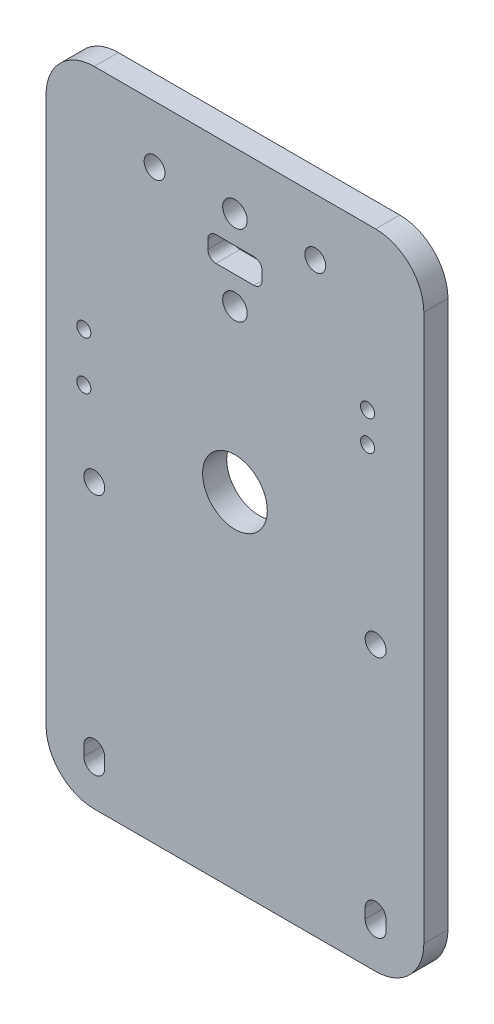
SolidWorks part; units mm, degrees
material "Acrylic (Medium-high impact)"
ref_plane "Спереди" through (0, 0, 0) normal (0, 0, 1) x (1, 0, 0)
ref_plane "Сверху" through (0, 0, 0) normal (0, 1, 0) x (1, 0, 0)
ref_plane "Справа" through (0, 0, 0) normal (1, 0, 0) x (0, 0, -1)
sketch "Model" plane through (0, 0, 0) normal (0, 0, 1) x (1, 0, 0)
  line L5 (0, 170.1561) -> (0, 0) construction
  line L24 (-35, 37.2847) -> (-35, 78.8619) construction
  line L25 (-31.4983, 12.5) -> (-38.4, 12.5) construction
  line L26 (-31.4983, 10) -> (-38.4, 10) construction
  line L27 (-35, 12.5) -> (-35, 10) construction
  line L28 (-32.4, 12.5) -> (-32.4, 10)
  line L29 (-37.6, 12.5) -> (-37.6, 10)
  line L40 (31.4983, 10) -> (38.4, 10) construction
  line L41 (31.4983, 12.5) -> (38.4, 12.5) construction
  line L42 (35, 37.2847) -> (35, 78.8619) construction
  line L43 (35, 12.5) -> (35, 10) construction
  line L44 (32.4, 12.5) -> (32.4, 10)
  line L45 (37.6, 12.5) -> (37.6, 10)
  line L47 (-26.0102, 145.8) -> (26.0946, 145.8) construction
  line L50 (-20, 133.6948) -> (-20, 127.8457) construction
  line L51 (-38.85, 70.45) -> (-29.8907, 70.45) construction
  line L53 (-16.3166, 125.8) -> (17.7871, 125.8) construction
  line L58 (38.85, 70.45) -> (29.8907, 70.45) construction
  line L4875 (-35, 160) -> (35, 160)
  line L4882 (47, 148) -> (47, 12)
  line L4889 (35, 0) -> (-35, 0)
  line L4896 (-47, 12) -> (-47, 148)
  line L6648 (-6.75, 138.9) -> (6.75, 138.9)
  line L6649 (6.75, 138.9) -> (6.75, 132.7)
  line L6650 (6.75, 132.7) -> (-6.75, 132.7)
  line L6651 (-6.75, 132.7) -> (-6.75, 138.9)
  arc A0 (-47, 12) -> (-35, 0) centre (-35, 12) ccw
  arc A1 (35, 0) -> (47, 12) centre (35, 12) ccw
  arc A2 (47, 148) -> (35, 160) centre (35, 148) ccw
  arc A3 (-35, 160) -> (-47, 148) centre (-35, 148) ccw
  arc A13 (-32.4, 12.5) -> (-37.6, 12.5) centre (-35, 12.5) ccw
  arc A14 (-37.6, 10) -> (-32.4, 10) centre (-35, 10) ccw
  arc A19 (32.4, 12.5) -> (37.6, 12.5) centre (35, 12.5) cw
  arc A20 (37.6, 10) -> (32.4, 10) centre (35, 10) cw
  circle A29 centre (0, 145.8) radius 3.05
  circle A30 centre (-20, 145.8) radius 2.6
  circle A31 centre (20, 145.8) radius 2.6
  circle A32 centre (-35, 70.45) radius 2.6
  circle A33 centre (0, 125.8) radius 3.05
  circle A36 centre (35, 70.45) radius 2.6
  point P0 (-6.75, 135.8)
  point P17 (0, 0)
  point P77 (-35, 11.25)
  point P114 (35, 11.25)
  dimension "D35" = 6.1
  dimension "D5" = 5.2
  dimension "D2" = 70
  dimension "D3" = 160
  dimension "D15" = 12
  dimension "D16" = 2.5
  dimension "D17" = 10
  dimension "D18" = 5.2
  dimension "D25" = 14.2
  dimension "D34" = 20
  dimension "D42" = 6.2
  dimension "D9" = 70
  dimension "D10" = 57.95
  dimension "D6" = 20
  dimension "D7" = 20
  dimension "D8" = 13.5
  dimension "D11" = 10
extrude "Base" add sketch "Model" along normal blind 6 contours L4875 A3 L4896 A0 L4889 A1 L4882 A2 L45 A20 L44 A19 region at (0, 79.6161, 0)
sketch "Эскиз1" plane through (0, 0, 0) normal (0, 0, -1) x (-1, 0, 0)
  line L0 (35, 160) -> (-35, 160) construction
  line L1 (0, 160) -> (0, 146.8198) construction
  circle A0 centre (0, 85.8) radius 8.05
  dimension "D2" = 16.1
  dimension "D1" = 74.2
extrude "BearingHole" cut sketch "Эскиз1" against normal blind 10
sketch "Sketch1" plane through (0, 0, 6) normal (0, 0, 1) x (1, 0, 0)
  line L0 (-35, 160) -> (35, 160) construction
  line L1 (47, 148) -> (47, 12) construction
  circle A0 centre (33, 120) radius 1.75
  circle A1 centre (33, 112.5) radius 1.75
  dimension "D1" = 3.5
  dimension "D3" = 7.5
  dimension "D4" = 40
  dimension "D5" = 14
extrude "SensorMount" cut sketch "Sketch1" against normal blind 10
sketch "Sketch3" plane through (0, 0, 0) normal (0, 0, -1) x (-1, 0, 0)
  line L0 (-35, 0) -> (35, 0) construction
  line L1 (47, 12) -> (47, 148) construction
  circle A0 centre (37.6, 90.0886) radius 1.75
  circle A1 centre (37.6, 102.0886) radius 1.75
  dimension "D3" = 3.5
  dimension "D4" = 90.0886
  dimension "D1" = 12
  dimension "D2" = 9.4
extrude "CableMount" cut sketch "Sketch3" against normal blind 10
fillet "FilletCableSlot" radius 2 4 edges at (6.75, 138.9, 3) (-6.75, 138.9, 3) (-6.75, 132.7, 3) (6.75, 132.7, 3)
ref_plane "Plane1" through (0, 40.225, 0) normal (0, -1, 0) x (-1, 0, 0)
equation "\"D11@Model\"=\"D34@Model\"/2"
